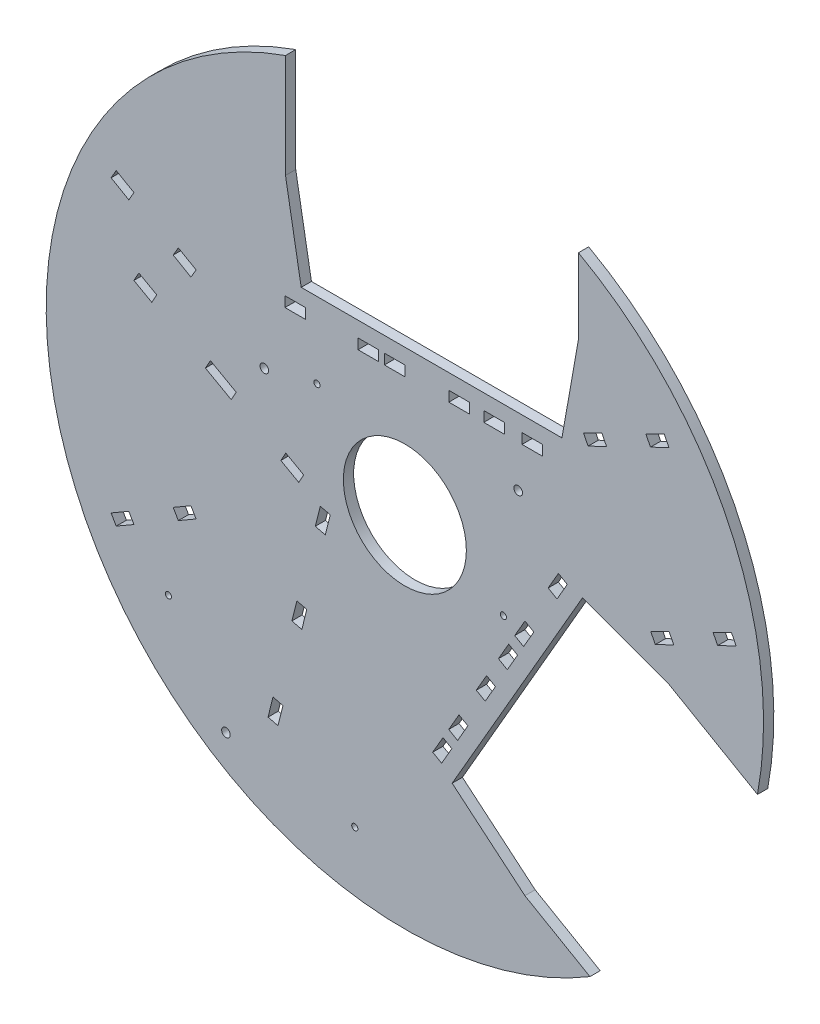
SolidWorks part; units mm, degrees
material "Balsa"
ref_plane "Plan de face" through (0, 0, 0) normal (0, 0, 1) x (1, 0, 0)
ref_plane "Plan de dessus" through (0, 0, 0) normal (0, 1, 0) x (1, 0, 0)
ref_plane "Plan de droite" through (0, 0, 0) normal (1, 0, 0) x (0, 0, -1)
sketch "Esquisse1" plane through (0, 0, 0) normal (0, 0, 1) x (1, 0, 0)
  circle A0 centre (0, 0) radius 175
  dimension "D1" = 350
extrude "Boss.-Extru.1" add sketch "Esquisse1" along normal blind 5
sketch "Esquisse2" plane through (0, 0, 0) normal (0, 0, -1) x (-1, 0, 0)
  line L0 (58.2408, 114.332) -> (58.2408, 213.8766)
  line L1 (58.2408, 213.8766) -> (-84.6817, 213.8766)
  line L2 (-84.6817, 213.8766) -> (-84.6817, 116.5135)
  line L3 (0, 0) -> (-290.6498, 0) construction
  line L4 (-84.6817, 116.5135) -> (-76.6366, 70.8876)
  line L5 (-76.6366, 70.8876) -> (50.5804, 70.8876)
  line L6 (50.5804, 70.8876) -> (58.2408, 114.332)
  line L7 (-128.1349, -6.728) -> (-214.343, -56.5003)
  line L8 (-214.343, -56.5003) -> (-142.8818, -180.2748)
  line L9 (-142.8818, -180.2748) -> (-58.5628, -131.5932)
  line L10 (-58.5628, -131.5932) -> (-23.0722, -101.8131)
  line L11 (-23.0722, -101.8131) -> (-86.6807, 8.3601)
  line L12 (-86.6807, 8.3601) -> (-128.1349, -6.728)
  point P16 (0, 0)
  point P43 (0, 0)
  dimension "D5" = 142.989
  dimension "D6" = 99.5446
  dimension "D1" = 127.217
  dimension "D2" = 100
  dimension "D3" = 100
  dimension "D4" = 142.9225
  dimension "D7" = 70.8876
  dimension "D8" = 50.5804
  dimension "D10" = 120
  dimension "D9" = 2
extrude "Enlèv. mat.-Extru.1" cut sketch "Esquisse2" against normal blind 5
sketch "Esquisse3" plane through (0, 0, 5) normal (0, 0, 1) x (1, 0, 0)
  line L0 (0, 0) -> (0, 103.8673) construction
  line L1 (-49.3567, -7.7578) -> (-58.0775, -2.8643)
  line L2 (-49.3567, -7.7578) -> (-51.8034, -12.1183)
  line L3 (-58.0775, -2.8643) -> (-60.5243, -7.2247)
  line L4 (-51.8034, -12.1183) -> (-60.5243, -7.2247)
  line L5 (-82.2991, 10.7274) -> (-94.8707, 17.7817)
  line L6 (-82.2991, 10.7274) -> (-84.7459, 6.3669)
  line L7 (-94.8707, 17.7817) -> (-97.3175, 13.4213)
  line L8 (-84.7459, 6.3669) -> (-97.3175, 13.4213)
  line L9 (-121.0332, 32.4625) -> (-129.754, 37.356)
  line L10 (-121.0332, 32.4625) -> (-123.48, 28.1021)
  line L11 (-129.754, 37.356) -> (-132.2008, 32.9956)
  line L12 (-123.48, 28.1021) -> (-132.2008, 32.9956)
  line L13 (-36.4119, -18.1392) -> (-38.8398, -27.84)
  line L14 (-36.4119, -18.1392) -> (-41.2623, -16.9253)
  line L15 (-38.8398, -27.84) -> (-43.6902, -26.6261)
  line L16 (0, 0) -> (104.6701, 42.2895) construction
  line L17 (-41.2623, -16.9253) -> (-43.6902, -26.6261)
  line L18 (-47.8487, -63.8364) -> (-50.2765, -73.5372)
  line L19 (-47.8487, -63.8364) -> (-52.6991, -62.6224)
  line L20 (-50.2765, -73.5372) -> (-55.1269, -72.3233)
  line L21 (-52.6991, -62.6224) -> (-55.1269, -72.3233)
  line L22 (-59.4765, -110.2968) -> (-61.9044, -119.9976)
  line L23 (-59.4765, -110.2968) -> (-64.3269, -109.0829)
  line L24 (-61.9044, -119.9976) -> (-66.7548, -118.7837)
  line L25 (-64.3269, -109.0829) -> (-66.7548, -118.7837)
  line L26 (62.9144, -18.0042) -> (58.5843, -15.5042)
  line L27 (62.9144, -18.0042) -> (57.9144, -26.6645)
  line L28 (58.5843, -15.5042) -> (53.5843, -24.1645)
  line L29 (57.9144, -26.6645) -> (53.5843, -24.1645)
  line L30 (39.8511, -47.9511) -> (44.1813, -50.4511)
  line L31 (39.8511, -47.9511) -> (34.8511, -56.6113)
  line L32 (44.1813, -50.4511) -> (39.1813, -59.1113)
  line L33 (34.8511, -56.6113) -> (39.1813, -59.1113)
  line L34 (18.5843, -84.7863) -> (22.9144, -87.2863)
  line L35 (18.5843, -84.7863) -> (13.5843, -93.4465)
  line L36 (22.9144, -87.2863) -> (17.9144, -95.9465)
  line L37 (13.5843, -93.4465) -> (17.9144, -95.9465)
  line L38 (23.0722, -101.8131) -> (86.6807, 8.3601) construction
  line L40 (67.1551, 63.3876) -> (57.1551, 63.3876)
  line L41 (67.1551, 63.3876) -> (67.1551, 58.3876)
  line L42 (67.1551, 58.3876) -> (57.1551, 58.3876)
  line L43 (57.1551, 63.3876) -> (57.1551, 58.3876)
  line L44 (-12.8449, 63.3876) -> (-22.8449, 63.3876)
  line L45 (-12.8449, 63.3876) -> (-12.8449, 58.3876)
  line L46 (-12.8449, 58.3876) -> (-22.8449, 58.3876)
  line L47 (-22.8449, 63.3876) -> (-22.8449, 58.3876)
  line L48 (31.4441, 63.3876) -> (21.4441, 63.3876)
  line L49 (31.4441, 63.3876) -> (31.4441, 58.3876)
  line L50 (31.4441, 58.3876) -> (21.4441, 58.3876)
  line L51 (21.4441, 63.3876) -> (21.4441, 58.3876)
  line L52 (76.6366, 70.8876) -> (-50.5804, 70.8876) construction
  line B0 (122.1484, 6.3102) -> (119.9636, 10.8076)
  line B1 (128.9584, 15.1772) -> (119.9636, 10.8076)
  line B2 (131.1432, 10.6797) -> (122.1484, 6.3102)
  line B3 (131.1432, 10.6797) -> (128.9584, 15.1772)
  line B4 (159.3791, 29.9551) -> (150.3842, 25.5855)
  line B5 (152.569, 21.0881) -> (150.3842, 25.5855)
  line B6 (161.5639, 25.4577) -> (159.3791, 29.9551)
  line B7 (161.5639, 25.4577) -> (152.569, 21.0881)
  line B8 (126.6073, 97.4163) -> (117.6125, 93.0467)
  line B9 (126.6073, 97.4163) -> (128.7921, 92.9189)
  line B10 (117.6125, 93.0467) -> (119.7973, 88.5493)
  line B11 (128.7921, 92.9189) -> (119.7973, 88.5493)
  line B12 (96.1867, 82.6383) -> (98.3714, 78.1409)
  line B13 (96.1867, 82.6383) -> (87.1918, 78.2688)
  line B14 (98.3714, 78.1409) -> (89.3766, 73.7714)
  line B15 (87.1918, 78.2688) -> (89.3766, 73.7714)
  line B16 (87.1918, 78.2688) -> (104.6701, 42.2895) construction
  dimension "D1" = 112.6276
  dimension "D2" = 68
  dimension "D3" = 5
  dimension "D4" = 5
  dimension "D5" = 30.9185
  dimension "D6" = 7.4
  dimension "D7" = 5
  dimension "D8" = 10
  dimension "D9" = 10
  dimension "D10" = 10
  dimension "D11" = 10
  dimension "D12" = 5
  dimension "D13" = 10
  dimension "D14" = 32.5336
  dimension "D15" = 10
  dimension "D16" = 27.4664
  dimension "D17" = 7.5
  dimension "D18" = 10
sketch_block_instance "Bloc1-1"
sketch_block "Bloc1" parameters "D1"=5, "D2"=23.8202, "D3"=40, "D4"=10, "D5"=10, "D6"=5
extrude "Enlèv. mat.-Extru.2" cut sketch "Esquisse3" against normal blind 10
sketch "Esquisse4" plane through (0, 0, 0) normal (0, 0, -1) x (-1, 0, 0)
  line L0 (42.8627, 33.9844) -> (-48.07, -18.5156) construction
  line L1 (42.8627, 33.9844) -> (115.3627, -91.5893) construction
  line L2 (-48.07, -18.5156) -> (24.43, -144.0893) construction
  line L3 (115.3627, -91.5893) -> (24.43, -144.0893) construction
  line L4 (-23.0722, -101.8131) -> (-86.6807, 8.3601) construction
  circle A0 centre (115.3627, -91.5893) radius 1.5
  circle A1 centre (24.43, -144.0893) radius 1.5
  circle A2 centre (-48.07, -18.5156) radius 1.5
  circle A3 centre (42.8627, 33.9844) radius 1.5
  dimension "D1" = 3
  dimension "D2" = 105
  dimension "D3" = 145
  dimension "D4" = 20
  dimension "D5" = 8
extrude "Enlèv. mat.-Extru.3" cut sketch "Esquisse4" against normal blind 10
sketch "Esquisse5" plane through (0, 0, 0) normal (0, 0, -1) x (-1, 0, 0)
  line L0 (132.1784, -70.1252) -> (134.6784, -65.7951)
  line L1 (132.1784, -70.1252) -> (140.8387, -75.1252)
  line L2 (134.6784, -65.7951) -> (143.3387, -70.7951)
  line L3 (140.8387, -75.1252) -> (143.3387, -70.7951)
  line L4 (110.5278, -57.6252) -> (113.0278, -53.2951)
  line L5 (110.5278, -57.6252) -> (101.8675, -52.6252)
  line L6 (113.0278, -53.2951) -> (104.3675, -48.2951)
  line L7 (101.8675, -52.6252) -> (104.3675, -48.2951)
  line L8 (134.6784, 65.7951) -> (132.1784, 70.1252)
  line L9 (134.6784, 65.7951) -> (143.3387, 70.7951)
  line L10 (132.1784, 70.1252) -> (140.8387, 75.1252)
  line L11 (143.3387, 70.7951) -> (140.8387, 75.1252)
  line L12 (110.5278, 57.6252) -> (113.0278, 53.2951)
  line L13 (110.5278, 57.6252) -> (101.8675, 52.6252)
  line L14 (113.0278, 53.2951) -> (104.3675, 48.2951)
  line L15 (101.8675, 52.6252) -> (104.3675, 48.2951)
  line L16 (134.6784, 65.7951) -> (113.0278, 53.2951) construction
  line L17 (143.3387, 70.7951) -> (104.3675, 48.2951) construction
  line L18 (143.3387, -70.7951) -> (104.3675, -48.2951) construction
  dimension "D1" = 10
  dimension "D2" = 115
  dimension "D3" = 25
  dimension "D4" = 25
  dimension "D5" = 5
  dimension "D6" = 115
extrude "Enlèv. mat.-Extru.4" cut sketch "Esquisse5" against normal blind 10
sketch "Esquisse6" plane through (0, 0, 5) normal (0, 0, 1) x (1, 0, 0)
  line L0 (20.7319, -91.0665) -> (84.2319, 18.9187) construction
  line L1 (25.7319, -82.4063) -> (30.7319, -73.746)
  line L2 (25.7319, -82.4063) -> (21.4018, -79.9063)
  line L3 (30.7319, -73.746) -> (26.4018, -71.246)
  line L4 (21.4018, -79.9063) -> (26.4018, -71.246)
  line L5 (49.9819, -40.4041) -> (54.9819, -31.7438)
  line L6 (49.9819, -40.4041) -> (45.6518, -37.9041)
  line L7 (54.9819, -31.7438) -> (50.6518, -29.2438)
  line L8 (45.6518, -37.9041) -> (50.6518, -29.2438)
  line L9 (52.4819, -36.0739) -> (43.8216, -31.0739) construction
  line L10 (58.5, 63.3876) -> (-68.5, 63.3876) construction
  line L11 (48.5, 63.3876) -> (38.5, 63.3876)
  line L12 (48.5, 63.3876) -> (48.5, 58.3876)
  line L14 (74.9018, 12.7584) -> (69.9018, 4.0982)
  line L15 (74.2319, 1.5982) -> (69.9018, 4.0982)
  line L16 (79.2319, 10.2584) -> (74.9018, 12.7584)
  line L17 (79.2319, 10.2584) -> (74.2319, 1.5982)
  line L20 (57.9144, -26.6645) -> (62.9144, -18.0042) construction
  line L21 (38.5, 63.3876) -> (38.5, 58.3876)
  line L22 (48.5, 58.3876) -> (38.5, 58.3876)
  line L23 (0, 63.3876) -> (-10, 63.3876)
  line L24 (0, 63.3876) -> (0, 58.3876)
  line L25 (-10, 63.3876) -> (-10, 58.3876)
  line L26 (0, 58.3876) -> (-10, 58.3876)
  line L27 (-5, 63.3876) -> (-5, 53.3876) construction
  line L29 (-58.5, 58.3876) -> (-48.5, 58.3876)
  line L30 (-48.5, 63.3876) -> (-48.5, 58.3876)
  line L31 (-58.5, 63.3876) -> (-58.5, 58.3876)
  line L32 (-58.5, 63.3876) -> (-48.5, 63.3876)
  line L33 (67.1551, 63.3876) -> (57.1551, 63.3876) construction
  dimension "D1" = 127
  dimension "D2" = 10
  dimension "D3" = 10
  dimension "D4" = 5
  dimension "D5" = 5
  dimension "D6" = 10
  dimension "D7" = 127
  dimension "D8" = 10
  dimension "D9" = 10
  dimension "D10" = 5
  dimension "D11" = 10
  dimension "D12" = 5
extrude "Enlèv. mat.-Extru.5" cut sketch "Esquisse6" against normal blind 5
hole_wizard "Trou taraudé M51" positions "Esquisse8" profile "Esquisse9" tap size "M5" standard "ISO" end condition through all
sketch "Esquisse8" plane through (0, 0, -85) normal (0, 0, -1) x (1, 0, 0)
  point P0 (-68.569, -27.6625)
  point P2 (55.2809, -37.9834)
  point P4 (-87.2993, 135.5593)
sketch "Esquisse9" plane through (-68.569, 27.6625, -85) normal (1, 0, 0) x (0, 1, 0)
  line L0 (0, 0) -> (0, 90)
  line L1 (0, 90) -> (2.1, 90)
  line L2 (2.1, 90) -> (2.1, 0)
  line L3 (2.1, 0) -> (0, 0)
  line L4 (0, -6.35) -> (0, 107.95) construction
  dimension "Diamètre principal du filetage" = 4.2
  dimension "Profondeur du trou pour taraudage jusqu'au prochain" = 90
sketch "Esquisse10" plane through (0, 0, 5) normal (0, 0, 1) x (1, 0, 0)
  circle A0 centre (0, 0) radius 30
extrude "Enlèv. mat.-Extru.6" cut sketch "Esquisse10" against normal blind 5
